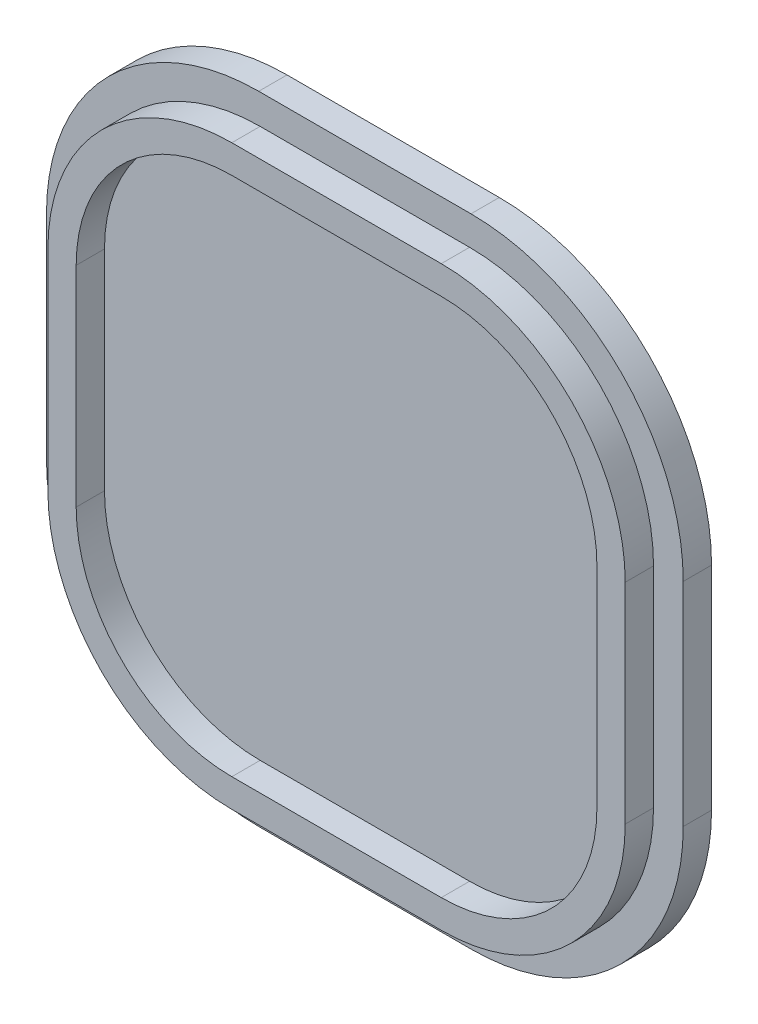
SolidWorks part; units mm, degrees
ref_plane "정면" through (0, 0, 0) normal (0, 0, 1) x (1, 0, 0)
ref_plane "윗면" through (0, 0, 0) normal (0, 1, 0) x (1, 0, 0)
ref_plane "우측면" through (0, 0, 0) normal (1, 0, 0) x (0, 0, -1)
sketch "스케치1" plane through (0, 0, 0) normal (0, 0, 1) x (1, 0, 0)
  line L1 (-11.2202, 18.4032) -> (33.7798, 18.4032)
  line L2 (-11.2202, 18.4032) -> (-11.2202, -26.5968)
  line L3 (-11.2202, -26.5968) -> (33.7798, -26.5968)
  line L4 (33.7798, 18.4032) -> (33.7798, -26.5968)
  dimension "D1" = 45
  dimension "D2" = 45
extrude "보스-돌출1" add sketch "스케치1" along normal blind 2
fillet "필렛1" radius 15 4 edges at (33.7798, -26.5968, 1) (-11.2202, -26.5968, 1) (-11.2202, 18.4032, 1) (33.7798, 18.4032, 1)
sketch "스케치2" plane through (0, 0, 2) normal (0, 0, 1) x (1, 0, 0)
  line L0 (11.2798, 18.4032) -> (11.2798, -26.5968) construction
  line L1 (18.7798, 18.4032) -> (3.7798, 18.4032) construction
  line L2 (3.7798, -26.5968) -> (18.7798, -26.5968) construction
  line L4 (-9.1202, 16.3032) -> (31.6798, 16.3032)
  line L5 (-9.1202, 16.3032) -> (-9.1202, -24.4968)
  line L6 (-9.1202, -24.4968) -> (31.6798, -24.4968)
  line L7 (31.6798, 16.3032) -> (31.6798, -24.4968)
  line L8 (-9.1202, 16.3032) -> (31.6798, -24.4968) construction
  line L9 (-9.1202, -24.4968) -> (31.6798, 16.3032) construction
  point P6 (11.2798, -4.0968)
  dimension "D1" = 40.8
  dimension "D2" = 40.8
extrude "보스-돌출2" add sketch "스케치2" along normal blind 2
fillet "필렛2" radius 13 4 edges at (31.6798, -24.4968, 3) (-9.1202, -24.4968, 3) (-9.1202, 16.3032, 3) (31.6798, 16.3032, 3)
shell "쉘1" thickness 2 removed face at (11.2798, -4.0968, 4)
